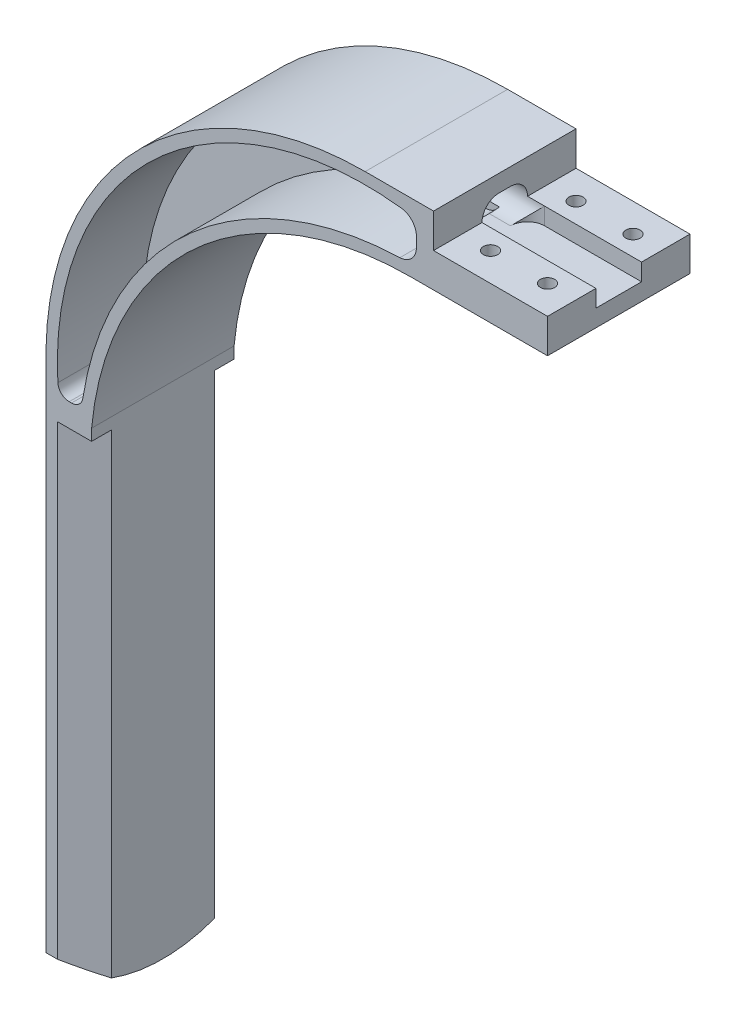
SolidWorks part; units mm, degrees
material "Сплав 2024"
ref_plane "Спереди" through (0, 0, 0) normal (0, 0, 1) x (1, 0, 0)
ref_plane "Сверху" through (0, 0, 0) normal (0, 1, 0) x (1, 0, 0)
ref_plane "Справа" through (0, 0, 0) normal (1, 0, 0) x (0, 0, -1)
sketch "Эскиз1" plane through (0, 0, 0) normal (0, 0, 1) x (1, 0, 0)
  line L0 (0, 0) -> (0, 95)
  line L1 (0, 0) -> (8, 0)
  line L2 (-20.7345, 150) -> (144.5665, 150) construction
  line L3 (88, 163.3115) -> (88, 122.0175) construction
  line L4 (8, 0) -> (8, 87)
  line L6 (88, 150) -> (56, 150)
  line L7 (88, 150) -> (88, 138)
  line L8 (88, 138) -> (64, 138)
  arc A0 (64, 138) -> (8, 87) centre (64, 81.7549) ccw
  arc A1 (56, 150) -> (0, 95) centre (56, 93.9909) ccw
  dimension "D1" = 95
  dimension "D2" = 87
  dimension "D3" = 150
  dimension "D4" = 88
  dimension "D5" = 8
  dimension "D6" = 12
  dimension "D7" = 32
  dimension "D8" = 24
extrude "Бобышка-Вытянуть1" add sketch "Эскиз1" along normal blind 25
sketch "Эскиз2" plane through (0, 0, 25) normal (0, 0, 1) x (1, 0, 0)
  line L1 (88, 150) -> (68, 150)
  line L2 (88, 150) -> (88, 144)
  line L3 (88, 144) -> (68, 144)
  line L4 (68, 150) -> (68, 144)
  dimension "D1" = 20
  dimension "D2" = 6
extrude "Вырез-Вытянуть1" cut sketch "Эскиз2" against normal through all
sketch "Эскиз5" plane through (0, 0, 0) normal (0, -1, 0) x (1, 0, 0)
  line L0 (8, 3.4641) -> (2, 0)
  line L1 (8, 25) -> (8, 0) construction
  line L2 (8, 3.4641) -> (10.1941, 4.7308)
  line L3 (2, 0) -> (8, 0)
  line L4 (8, 0) -> (8, 3.4641) construction
  line L5 (0, 25) -> (0, 0) construction
  line L6 (8, 12.5) -> (7.5, 12.5) construction
  line L7 (8, 25) -> (8, 0) construction
  line L8 (8, 25) -> (8, 21.5359) construction
  line L9 (2, 25) -> (8, 25)
  line L10 (8, 21.5359) -> (2, 25)
  line L11 (0, 0) -> (8, 0) construction
  line L12 (10.1941, 4.7308) -> (10.1941, 0)
  line L13 (8, 0) -> (64, 0) construction
  line L14 (10.1941, 0) -> (8, 0)
  line L15 (8, 21.5359) -> (10.1941, 20.2692)
  line L16 (10.1941, 20.2692) -> (10.1941, 25)
  line L17 (64, 25) -> (8, 25) construction
  line L18 (10.1941, 25) -> (8, 25)
  dimension "D1" = 2
  dimension "D2" = 60
extrude "Вырез-Вытянуть2" cut sketch "Эскиз5" against normal blind 85
sketch "Эскиз6" plane through (0, 0, 0) normal (-1, 0, 0) x (0, 0, 1)
  line L0 (12.5, 0) -> (12.5, 16.6862) construction
  line L1 (25, 0) -> (0, 0) construction
  line L2 (12.5, -11.9161) -> (12.5, 92.5) construction
  line L3 (10, -11.9161) -> (10, 92.5)
  line L4 (15, -11.9161) -> (15, 92.5)
  line L5 (25, 95) -> (0, 95) construction
  arc A0 (10, -11.9161) -> (15, -11.9161) centre (12.5, -11.9161) ccw
  arc A1 (15, 92.5) -> (10, 92.5) centre (12.5, 92.5) ccw
  point P7 (12.5, 40.292)
  dimension "D1" = 5
extrude "Вырез-Вытянуть4" cut sketch "Эскиз6" against normal blind 5
sketch "Эскиз3" plane through (0, 0, 25) normal (0, 0, -1) x (-1, 0, 0)
  line L0 (-65, 147.2448) -> (-65, 139.9914)
  line L1 (-68, 150) -> (-68, 144) construction
  line L2 (-6.2158, 89.0676) -> (-2.2158, 89.0676)
  arc A4 (-65, 147.2448) -> (-2.2158, 89.0676) centre (-56, 93.9909) cw
  arc A5 (-65, 139.9914) -> (-6.2158, 89.0676) centre (-64, 81.7549) cw
  arc A6 (0, 95) -> (-56, 150) centre (-56, 93.9909) ccw construction
  arc A7 (-8, 87) -> (-64, 138) centre (-64, 81.7549) ccw construction
  dimension "D1" = 2
  dimension "D2" = 2
  dimension "D3" = 3
  dimension "D4" = 4
extrude "Вырез-Вытянуть3" cut sketch "Эскиз3" along normal up to surface (15 mm away) up to face at (2.5, 46.25, 10)
fillet "Скругление3" radius 2 2 edges at (6.2158, 89.0676, 17.5) (2.2158, 89.0676, 20)
fillet "Скругление4" radius 3 2 edges at (65, 147.2448, 17.5) (65, 139.9914, 17.5)
ref_plane "Плоскость1" through (0, 10, 0) normal (0, 1, 0) x (1, 0, 0)
sketch "Эскиз8" plane through (0, 10, 0) normal (0, 1, 0) x (1, 0, 0)
  line L0 (0, -2) -> (1.5, -2)
  line L1 (0, -12.5) -> (0, 0) construction
  line L2 (1.5, -2) -> (1.5, -3)
  line L3 (3.5, -4) -> (5.5, -4)
  line L4 (5.5, -4) -> (5.5, -8)
  line L5 (5.5, -8) -> (0, -8)
  line L6 (0, -8) -> (0, -2)
  line L7 (56, 0) -> (0, 0) construction
  line L8 (2.0115, -10) -> (0, -10) construction
  line L9 (1.5, -3) -> (3.5, -3)
  line L10 (3.5, -3) -> (3.5, -4)
  line L11 (8, -25) -> (8, 0) construction
  line L12 (8, -12.5) -> (6.1534, -12.5) construction
  line L13 (3.5, -22) -> (3.5, -21)
  line L14 (1.5, -22) -> (3.5, -22)
  line L15 (0, -17) -> (0, -23)
  line L16 (5.5, -17) -> (0, -17)
  line L17 (5.5, -21) -> (5.5, -17)
  line L18 (3.5, -21) -> (5.5, -21)
  line L19 (1.5, -23) -> (1.5, -22)
  line L20 (0, -23) -> (1.5, -23)
  dimension "D1" = 2
  dimension "D2" = 2
  dimension "D3" = 4
  dimension "D4" = 1
  dimension "D5" = 1.5
  dimension "D6" = 2
  dimension "D7" = 2.5
extrude "Вырез-Вытянуть6" cut sketch "Эскиз8" along normal blind 75
sketch "Эскиз9" plane through (0, 144, 0) normal (0, 1, 0) x (1, 0, 0)
  line L0 (88, 0) -> (68, -25) construction
  line L1 (88, 0) -> (88, -25) construction
  line L2 (73, -5) -> (83, -5) construction
  line L3 (73, -5) -> (73, -20) construction
  line L4 (73, -20) -> (83, -20) construction
  line L5 (83, -5) -> (83, -20) construction
  line L6 (73, -5) -> (83, -20) construction
  line L7 (73, -20) -> (83, -5) construction
  line L8 (68, 0) -> (88, 0) construction
  point P4 (78, -12.5)
  dimension "D1" = 5
  dimension "D2" = 5
hole_wizard "Отверстие обработанное метчиком M3x0.51" positions "Эскиз11" profile "Эскиз10" tap size "M3x0.5" standard "Ansi Metric" end condition up to next
sketch "Эскиз11" plane through (19.192, 144, 18.7997) normal (0, 1, 0) x (1, 0, 0)
  point P0 (53.808, 13.7997)
  point P3 (63.808, 13.7997)
  point P6 (63.808, -1.2003)
  point P9 (53.808, -1.2003)
cosmetic thread "Отверстие резьбы2" parameters "D2"=3
cosmetic thread "Отверстие резьбы3" parameters "D2"=3
cosmetic thread "Отверстие резьбы4" parameters "D2"=3
cosmetic thread "Отверстие резьбы5" parameters "D2"=3
sketch "Эскиз10" plane through (73, 144, 5) normal (1, 0, 0) x (0, 0, 1)
  line L0 (0, 0) -> (0, 6)
  line L1 (0, 6) -> (1.25, 6)
  line L2 (1.25, 6) -> (1.25, 0)
  line L5 (1.25, 0) -> (0, 0)
  line L11 (0, -6.35) -> (0, 107.95) construction
  dimension "Диаметр проходного сверла" = 2.5
  dimension "Глубина проходного сверла" = 6
sketch "Эскиз12" plane through (0, 0, 0) normal (-1, 0, 0) x (0, 0, 1)
  line L0 (12.5, 0) -> (12.5, 6.3491) construction
  line L1 (10, 0) -> (15, 0) construction
  line L3 (0, 3.302) -> (0, 0)
  line L4 (0, 95) -> (0, 0) construction
  line L5 (0, 0) -> (12.5, 0)
  line L6 (12.5, 0) -> (25, 0)
  line L7 (25, 0) -> (25, 3.302)
  line L8 (25, 95) -> (25, 0) construction
  arc A0 (0, 3.302) -> (25, 3.302) centre (12.5, 26.1) ccw
  dimension "D1" = 52
  dimension "D2" = 26.1
extrude "Вырез-Вытянуть7" cut sketch "Эскиз12" against normal up to next
sketch "Эскиз13" plane through (0, 144, 0) normal (0, 1, 0) x (1, 0, 0)
  line L0 (88, -12.5) -> (68, -12.5) construction
  line L1 (88, 0) -> (88, -25) construction
  line L2 (68, 0) -> (68, -25) construction
  line L4 (68, -8.5) -> (88, -8.5)
  line L5 (68, -8.5) -> (68, -16.5)
  line L6 (68, -16.5) -> (88, -16.5)
  line L7 (88, -8.5) -> (88, -16.5)
  line L8 (68, -8.5) -> (88, -16.5) construction
  line L9 (68, -16.5) -> (88, -8.5) construction
  point P6 (78, -12.5)
  dimension "D1" = 8
extrude "Вырез-Вытянуть8" cut sketch "Эскиз13" against normal blind 3
fillet "Скругление8" radius 3 2 edges at (68, 142.5, 8.5) (68, 142.5, 16.5)
sketch "Эскиз14" plane through (88, 0, 0) normal (1, 0, 0) x (0, 0, -1)
  line L0 (-12.5, 141) -> (-12.5, 154.1514) construction
  line L1 (-16.5, 141) -> (-8.5, 141) construction
  line L4 (-13.5, 144) -> (-11.5, 144) construction
  line L5 (-13.5, 147) -> (-11.5, 147)
  line L6 (-13.5, 141) -> (-11.5, 141)
  line L7 (-16.5, 141) -> (-16.5, 144) construction
  arc A0 (-13.5, 147) -> (-13.5, 141) centre (-13.5, 144) ccw
  arc A1 (-11.5, 141) -> (-11.5, 147) centre (-11.5, 144) ccw
  point P5 (-12.5, 144)
  dimension "D1" = 6
extrude "Вырез-Вытянуть9" cut sketch "Эскиз14" against normal blind 28
sketch "Эскиз15" plane through (0, 0, 0) normal (-1, 0, 0) x (0, 0, 1)
  line L0 (12.5, 92.5) -> (12.5, 85.5) construction
  line L1 (15, 92.5) -> (15, 85.5)
  line L2 (10, 92.5) -> (10, 85.5)
  line L3 (15, 0.2205) -> (15, 89.1366) construction
  arc A0 (15, 92.5) -> (10, 92.5) centre (12.5, 92.5) ccw
  arc A1 (10, 85.5) -> (15, 85.5) centre (12.5, 85.5) ccw
  point P3 (12.5, 89)
  dimension "D1" = 7
extrude "Вырез-Вытянуть10" cut sketch "Эскиз15" against normal blind 6
sketch "Эскиз19" plane through (0, 0, 0) normal (-1, 0, 0) x (0, 0, 1)
  line L0 (10, 85.5) -> (10, 0.2205) construction
  line L1 (15, 92.5) -> (15, 0.2205) construction
  line L2 (10, 10.1) -> (10, 0.2205)
  line L3 (15, 10.1) -> (15, 0.2205)
  line L4 (10, 10.1) -> (15, 10.1)
  arc A0 (10, 0.2205) -> (15, 0.2205) centre (12.5, 26.1) ccw construction
  arc A1 (10, 0.2205) -> (15, 0.2205) centre (12.5, 26.1) ccw
  dimension "D1" = 16
extrude "Бобышка-Вытянуть2" add sketch "Эскиз19" against normal up to surface (5 mm away) up to face at (5, 42.2051, 12.5)
sketch "Эскиз16" plane through (0, 0, 0) normal (-1, 0, 0) x (0, 0, 1)
  line L0 (25, 5.1) -> (0, 5.1) construction
  line L1 (25, 95) -> (25, 3.302) construction
  line L3 (0, 95) -> (0, 3.302) construction
  arc A0 (0, 3.302) -> (25, 3.302) centre (12.5, 26.1) ccw construction
  point P4 (12.5, 0.1)
  dimension "D1" = 5
hole_wizard "Отверстие обработанное метчиком M3x0.52" positions "Эскиз18" profile "Эскиз17" tap size "M3x0.5" standard "Ansi Metric"
sketch "Эскиз18" plane through (0, 0, 0) normal (-1, 0, 0) x (0, 0, 1)
  line L1 (25, 5.1) -> (0, 5.1) construction
  point P5 (12.5, 5.1)
sketch "Эскиз17" plane through (0, 5.1, 12.5) normal (0, 1, 0) x (0, 0, 1)
  line L0 (0, 0) -> (0, 4.7511)
  line L1 (0, 4.7511) -> (1.25, 4)
  line L2 (1.25, 4) -> (1.25, 0)
  line L5 (1.25, 0) -> (0, 0)
  line L10 (0, 4.7511) -> (-1.25, 4) construction
  line L11 (0, -6.35) -> (0, 107.95) construction
  dimension "Диаметр сверла" = 2.5
  dimension "Глубина сверла" = 4
  dimension "Угол заточки сверла" = 118
cosmetic thread "Отверстие резьбы1" parameters "D1"=4, "D2"=3
equation "\"D7@Эскиз1\"=27+5"
equation "\"D8@Эскиз1\"=19+5"
equation "\"D4@Эскиз1\"=83+5"
